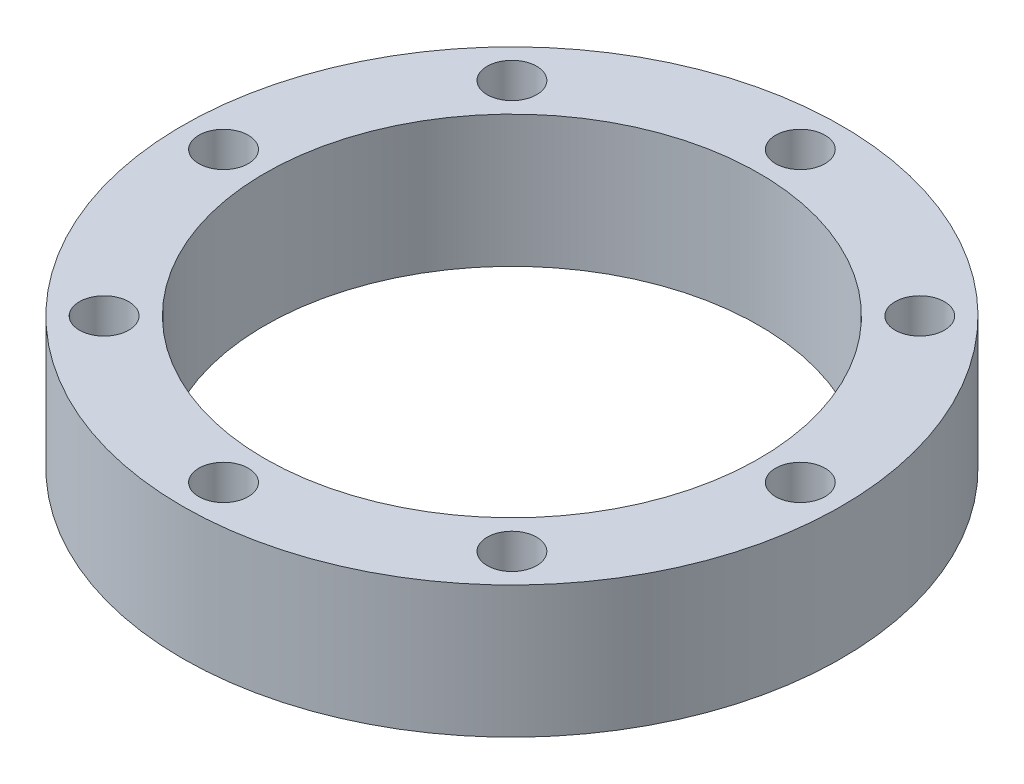
SolidWorks part; units mm, degrees
ref_plane "前视基准面" through (0, 0, 0) normal (0, 0, 1) x (1, 0, 0)
ref_plane "上视基准面" through (0, 0, 0) normal (0, 1, 0) x (1, 0, 0)
ref_plane "右视基准面" through (0, 0, 0) normal (1, 0, 0) x (0, 0, -1)
other "Configuration Table"
sketch "草图1" plane through (0, 0, 0) normal (0, 1, 0) x (1, 0, 0)
  circle A0 centre (0, 0) radius 15
  circle A1 centre (0, 0) radius 20
  circle A3 centre (0, 17.5) radius 1.5
  circle A4 centre (12.3744, 12.3744) radius 1.5
  circle A5 centre (17.5, 0) radius 1.5
  circle A6 centre (12.3744, -12.3744) radius 1.5
  circle A7 centre (0, -17.5) radius 1.5
  circle A8 centre (-12.3744, -12.3744) radius 1.5
  circle A9 centre (-17.5, 0) radius 1.5
  circle A10 centre (-12.3744, 12.3744) radius 1.5
  point P24 (0, 0)
  dimension "D1" = 30
  dimension "D2" = 40
  dimension "D4" = 3
  dimension "D5" = 8
extrude "凸台-拉伸1" add sketch "草图1" along normal blind 8
